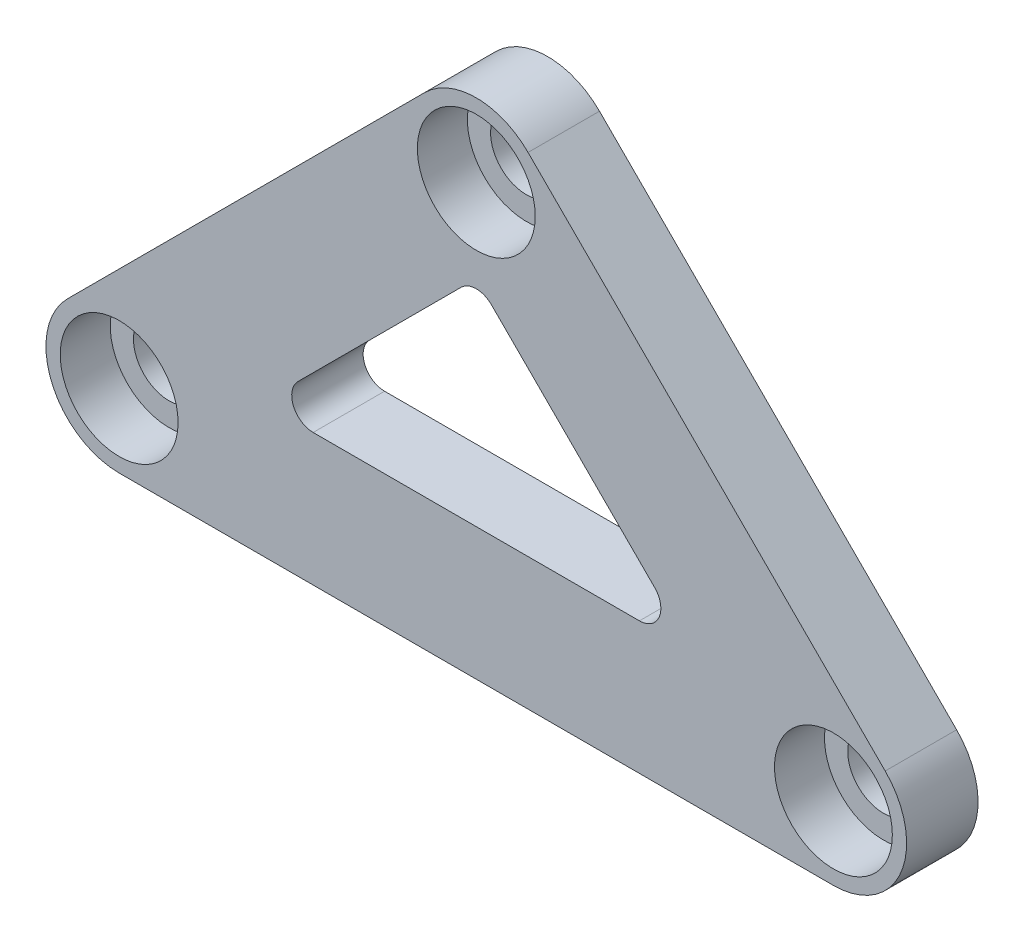
SolidWorks part; units mm, degrees
ref_plane "Front Plane" through (0, 0, 0) normal (0, 0, 1) x (1, 0, 0)
ref_plane "Top Plane" through (0, 0, 0) normal (0, 1, 0) x (1, 0, 0)
ref_plane "Right Plane" through (0, 0, 0) normal (1, 0, 0) x (0, 0, -1)
sketch "Sketch1" plane through (0, 0, 0) normal (0, 0, 1) x (1, 0, 0)
  line L0 (0, 0) -> (100, 0) construction
  line L1 (0, 10.25) -> (100, 10.25)
  line L2 (0, -10.25) -> (100, -10.25)
  line L3 (100, 0) -> (50, 50) construction
  line L4 (92.7522, -7.2478) -> (42.7522, 42.7522)
  line L5 (107.2478, 7.2478) -> (57.2478, 57.2478)
  line L6 (50, 50) -> (0, 0) construction
  line L7 (57.2478, 42.7522) -> (7.2478, -7.2478)
  line L8 (42.7522, 57.2478) -> (-7.2478, 7.2478)
  arc A0 (0, 10.25) -> (0, -10.25) centre (0, 0) ccw
  arc A1 (100, -10.25) -> (100, 10.25) centre (100, 0) ccw
  arc A2 (92.7522, -7.2478) -> (107.2478, 7.2478) centre (100, 0) ccw
  arc A3 (57.2478, 57.2478) -> (42.7522, 42.7522) centre (50, 50) ccw
  arc A4 (57.2478, 42.7522) -> (42.7522, 57.2478) centre (50, 50) ccw
  arc A5 (-7.2478, 7.2478) -> (7.2478, -7.2478) centre (0, 0) ccw
  point P2 (50, 0)
  point P7 (75, 25)
  point P14 (25, 25)
  point P21 (0, 0)
  dimension "D1" = 20.5
  dimension "D2" = 45
  dimension "D3" = 45
  dimension "D4" = 100
extrude "Boss-Extrude1" add sketch "Sketch1" along normal blind 10 contours A4 L7 L4 L1 A1 L5 | L4 A2 A1 L1 | A5 L2 A2 L4 L1 L7 | L7 A5 L8 A4 region at (50, -1.0132, 0) region at (74.0722, 27.272, 0) region at (96.1173, 1.6083, 0)
sketch "Sketch2" plane through (0, 0, 10) normal (0, 0, 1) x (1, 0, 0)
  circle A0 centre (50, 50) radius 8.25
  circle A1 centre (100, 0) radius 8.25
  circle A2 centre (0, 0) radius 8.25
  arc A4 (-7.2478, 7.2478) -> (0, -10.25) centre (0, 0) ccw construction
  arc A5 (57.2478, 57.2478) -> (42.7522, 57.2478) centre (50, 50) ccw construction
  arc A6 (100, -10.25) -> (107.2478, 7.2478) centre (100, 0) ccw construction
  dimension "D1" = 16.5
  dimension "D2" = 16.5
  dimension "D3" = 16.5
extrude "Cut-Extrude1" cut sketch "Sketch2" against normal blind 7
sketch "Sketch4" plane through (0, 0, 10) normal (0, 0, 1) x (1, 0, 0)
  line L0 (19.9173, 8.25) -> (80.0827, 8.25)
  line L1 (80.0827, 8.25) -> (50, 38.3327)
  line L2 (50, 38.3327) -> (19.9173, 8.25)
  circle A0 centre (0, 0) radius 8.25 construction
  circle A1 centre (0, 0) radius 8.25 construction
  circle A2 centre (100, 0) radius 8.25 construction
  point P5 (49.5015, 39.2086)
  point P10 (50, 37.8376)
  dimension "D1" = 45
extrude "Cut-Extrude2" cut sketch "Sketch4" against normal blind 16
fillet "Fillet2" radius 3 3 edges at (80.0827, 8.25, 5) (19.9173, 8.25, 5) (50, 38.3327, 5)
sketch "Sketch5" plane through (0, 0, 10) normal (0, 0, 1) x (1, 0, 0)
  circle A0 centre (0, 0) radius 5
  circle A1 centre (50, 50) radius 5
  circle A2 centre (100, 0) radius 5
  circle A3 centre (100, 0) radius 8.25 construction
  circle A4 centre (0, 0) radius 8.25 construction
  circle A5 centre (50, 50) radius 8.25 construction
  dimension "D1" = 10
  dimension "D2" = 10
  dimension "D3" = 10
extrude "Cut-Extrude3" cut sketch "Sketch5" against normal blind 16
equation "\"D3@Sketch1\"=\"D2@Sketch1\""
equation "\"D2@Sketch2\"=\"D1@Sketch2\""
equation "\"D3@Sketch2\"=\"D2@Sketch2\""
equation "\"D2@Sketch5\"=\"D1@Sketch5\""
equation "\"D3@Sketch5\"=\"D1@Sketch5\""
